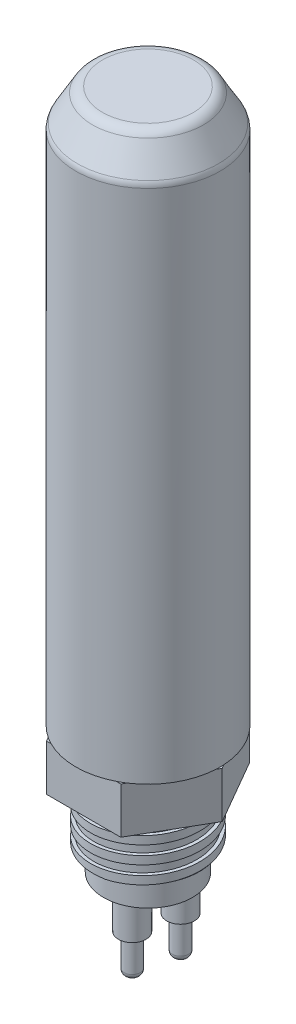
SolidWorks part; units mm, degrees
ref_plane "Front Plane" through (0, 0, 0) normal (0, 0, 1) x (1, 0, 0)
ref_plane "Top Plane" through (0, 0, 0) normal (0, 1, 0) x (1, 0, 0)
ref_plane "Right Plane" through (0, 0, 0) normal (1, 0, 0) x (0, 0, -1)
sketch "Sketch1" plane through (0, 0, 0) normal (0, 0, 1) x (1, 0, 0)
  line L0 (0, 0) -> (0, 99.5049) construction
  line L1 (-12.5, 93.5049) -> (-12.5, 3.5049)
  line L2 (-12.5, 3.5049) -> (0, 3.5049)
  line L3 (0, 99.5049) -> (0, 3.5049)
  line L4 (0, 99.5049) -> (-9.0491, 99.5049)
  line L5 (-9.0491, 99.5049) -> (-12.5, 93.5049)
  dimension "D1" = 90
  dimension "D3" = 6
  dimension "D2" = 12.5
revolve "Revolve1" add sketch "Sketch1" angle 360 about L0
sketch "Sketch2" plane through (0, 3.5049, 0) normal (0, -1, 0) x (1, 0, 0)
  line L1 (12.8749, 0) -> (6.4375, 11.15)
  line L2 (6.4375, 11.15) -> (-6.4375, 11.15)
  line L3 (-6.4375, 11.15) -> (-12.8749, 0)
  line L4 (-12.8749, 0) -> (-6.4375, -11.15)
  line L5 (-6.4375, -11.15) -> (6.4375, -11.15)
  line L6 (6.4375, -11.15) -> (12.8749, 0)
  circle A0 centre (0, 0) radius 11.15 construction
extrude "Boss-Extrude1" add sketch "Sketch2" along normal blind 8
sketch "Sketch3" plane through (0, -4.4951, 0) normal (0, -1, 0) x (1, 0, 0)
  circle A0 centre (0, 0) radius 9.5
extrude "Boss-Extrude2" add sketch "Sketch3" along normal blind 9.5
sketch3d "3DSketch1"
  line L1 (-9.5, -13.4418, 0) -> (-8.9227, -13.4418, 0)
  line L2 (-9.5, -13.4418, 0) -> (-9.5, -11.8418, 0)
  line L3 (-9.5, -11.8418, 0) -> (-8.9227, -11.8418, 0)
  line L4 (-8.9227, -13.4418, 0) -> (-8.9227, -11.8418, 0)
  dimension "D1" = 1.6
sketch "Sketch7" plane through (0, -13.9951, 0) normal (0, -1, 0) x (1, 0, 0)
  circle A0 centre (0, 0) radius 9.5
curve "Helix/Spiral1" pitch 3 height 12 turns 4
sweep "Cut-Sweep1" cut profiles "3DSketch1" path "Helix/Spiral1" align with end faces yes
sketch "Sketch14" plane through (0, -13.9951, 0) normal (0, -1, 0) x (1, 0, 0)
  circle A0 centre (0, 0) radius 7.7
extrude "Boss-Extrude3" add sketch "Sketch14" along normal blind 4.5
sketch "Sketch15" plane through (0, -18.4951, 0) normal (0, -1, 0) x (1, 0, 0)
  circle A0 centre (1.5581, 4.2922) radius 2.4
  circle A1 centre (2.9893, -2.6578) radius 2.4
  circle A2 centre (-3.9447, -2.1862) radius 2.4
  circle A3 centre (0, 0) radius 7.7 construction
  dimension "D6" = 4.8
  dimension "D1" = 6.95
  dimension "D2" = 6.95
  dimension "D3" = 8.5
  dimension "D4" = 4
  dimension "D5" = 4.51
extrude "Boss-Extrude4" add sketch "Sketch15" along normal blind 6
sketch "Sketch16" plane through (0, -24.4951, 0) normal (0, -1, 0) x (1, 0, 0)
  circle A0 centre (-3.9447, -2.1862) radius 1.4
  circle A1 centre (-3.9447, -2.1862) radius 2.4 construction
  circle A2 centre (2.9893, -2.6578) radius 1.4
  circle A3 centre (2.9893, -2.6578) radius 2.4 construction
  circle A4 centre (1.5581, 4.2922) radius 1.4
  circle A5 centre (1.5581, 4.2922) radius 2.4 construction
  dimension "D1" = 2.8
extrude "Boss-Extrude5" add sketch "Sketch16" along normal blind 6.5
fillet "Fillet1" radius 1 3 edges at (2.9893, -30.9951, -4.0578) (1.5581, -30.9951, 2.8922) (-3.9447, -30.9951, -3.5862)
other "Parting Line2" [suppressed]
other "Parting Surface1" [suppressed] parameters "D1"=10
sketch "Sketch17" [suppressed] plane through (0, 0, 0) normal (1, 0, 0) x (0, 0, -1)
  line L1 (24.2073, -5.3557) -> (-22.8755, -5.3557)
  line L2 (24.2073, -5.3557) -> (24.2073, 89.2486)
  line L3 (24.2073, 89.2486) -> (-22.8755, 89.2486)
  line L4 (-22.8755, -5.3557) -> (-22.8755, 89.2486)
fillet "Fillet2" radius 2 2 edges at (9.0491, 99.5049, 0) (12.5, 93.5049, 0)
